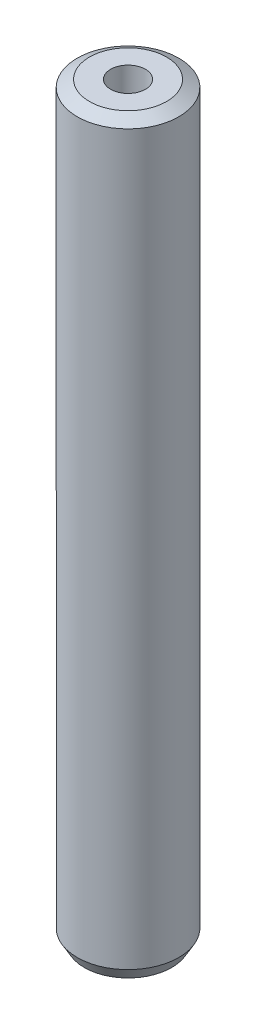
SolidWorks part; units mm, degrees
ref_plane "Front Plane" through (0, 0, 0) normal (0, 0, 1) x (1, 0, 0)
ref_plane "Top Plane" through (0, 0, 0) normal (0, 1, 0) x (1, 0, 0)
ref_plane "Right Plane" through (0, 0, 0) normal (1, 0, 0) x (0, 0, -1)
sketch "Sketch1" plane through (0, 0, 0) normal (0, 1, 0) x (1, 0, 0)
  circle A0 centre (0, 0) radius 22.5
  dimension "SHAFT_OD" = 45
extrude "Boss-Extrude1" add sketch "Sketch1" along normal blind 331.0052
sketch "Sketch2" plane through (0, 0, 0) normal (0, 1, 0) x (1, 0, 0)
  circle A0 centre (0, 0) radius 7.7025
  dimension "BORE_D" = 15.405
extrude "Cut-Extrude1" cut sketch "Sketch2" along normal through all
chamfer "Chamfer1" distance 3.1326 angle 60 2 edges at (0, 331.0052, 22.5) (0, 0, 22.5) first distance on face at (0, 331.0052, 22.5) first distance on face at (0, 0, 7.7025)
